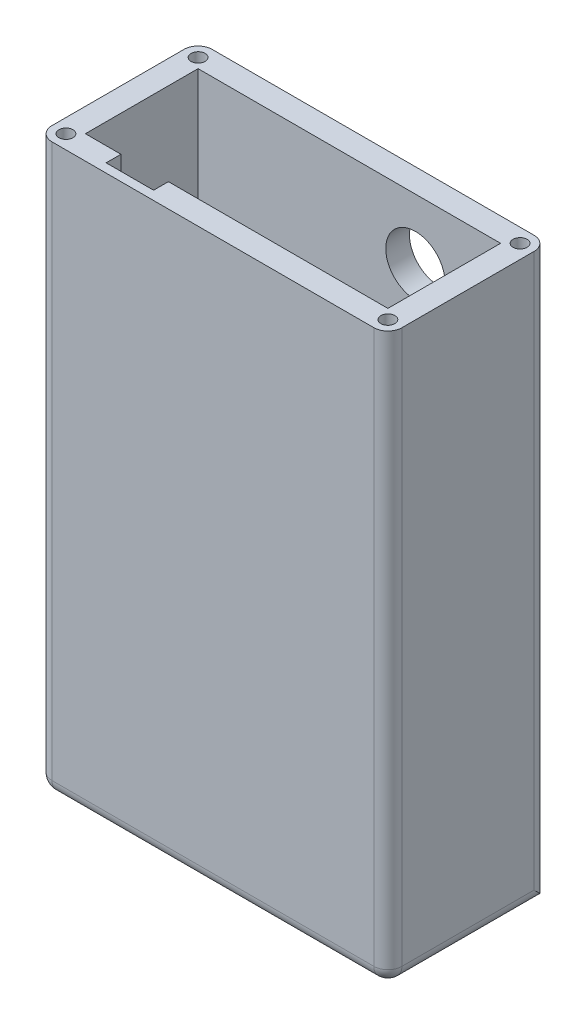
SolidWorks part; units mm, degrees
ref_plane "Front Plane" through (0, 0, 0) normal (0, 0, 1) x (1, 0, 0)
ref_plane "Top Plane" through (0, 0, 0) normal (0, 1, 0) x (1, 0, 0)
ref_plane "Right Plane" through (0, 0, 0) normal (1, 0, 0) x (0, 0, -1)
sketch "Sketch1" plane through (0, 0, 0) normal (0, 1, 0) x (1, 0, 0)
  line L1 (0, 0) -> (74.93, 0)
  line L2 (0, 0) -> (0, 34.29)
  line L3 (0, 34.29) -> (74.93, 34.29)
  line L4 (74.93, 0) -> (74.93, 34.29)
  dimension "D1" = 74.93
  dimension "D2" = 34.29
extrude "Boss-Extrude1" add sketch "Sketch1" along normal blind 87.122
shell "Shell1" thickness 2.54 removed face at (37.465, 43.561, -34.29)
sketch "Sketch12" plane through (0, 87.122, 0) normal (0, 1, 0) x (1, 0, 0)
  line L1 (0, 0) -> (74.93, 0)
  line L2 (0, 0) -> (0, 34.29)
  line L3 (0, 34.29) -> (74.93, 34.29)
  line L4 (74.93, 0) -> (74.93, 34.29)
extrude "Boss-Extrude6" add sketch "Sketch12" along normal blind 34.29
shell "Shell2" thickness 5.08 removed face at (37.465, 121.412, -17.145)
sketch "Sketch18" plane through (0, 89.662, 0) normal (0, 1, 0) x (1, 0, 0)
  line L0 (5.08, 5.08) -> (69.85, 5.08) construction
  line L1 (34.925, 5.08) -> (22.225, 5.08)
  line L2 (34.925, 5.08) -> (34.925, 14.605)
  line L3 (34.925, 14.605) -> (22.225, 14.605)
  line L4 (22.225, 5.08) -> (22.225, 14.605)
  line L5 (69.85, 5.08) -> (69.85, 29.21) construction
  line L6 (69.85, 29.21) -> (5.08, 29.21) construction
  line L7 (69.85, 22.21) -> (64.85, 22.21)
  line L8 (69.85, 22.21) -> (69.85, 12.08)
  line L9 (69.85, 12.08) -> (64.85, 12.08)
  line L10 (64.85, 22.21) -> (64.85, 12.08)
  dimension "D1" = 34.925
  dimension "D2" = 47.625
  dimension "D3" = 9.525
  dimension "D4" = 5
  dimension "D5" = 7
  dimension "D6" = 7
extrude "Cut-Extrude13" cut sketch "Sketch18" against normal up to next
sketch "Sketch20" plane through (0, 121.412, 0) normal (0, 1, 0) x (1, 0, 0)
  line L0 (0, 34.29) -> (0, 0) construction
  line L2 (74.93, 34.29) -> (0, 34.29) construction
  line L3 (0, 0) -> (74.93, 0) construction
  line L4 (74.93, 0) -> (74.93, 34.29) construction
  circle A0 centre (3, 31.29) radius 1.5
  circle A1 centre (3, 3) radius 1.5
  circle A2 centre (71.93, 3) radius 1.5
  circle A3 centre (71.93, 31.29) radius 1.5
  dimension "D1" = 3
  dimension "D2" = 3
  dimension "D3" = 3
  dimension "D4" = 3
  dimension "D5" = 3
  dimension "D6" = 3
  dimension "D7" = 3
  dimension "D8" = 3
extrude "Cut-Extrude14" cut sketch "Sketch20" against normal blind 20
fillet "Fillet1" radius 3 7 edges at (74.93, 0, -17.145) (0, 0, -17.145) (37.465, 0, 0) (74.93, 60.706, -34.29) (0, 60.706, -34.29) (74.93, 60.706, 0) (0, 60.706, 0)
sketch "Sketch22" plane through (0, 121.412, 0) normal (0, 1, 0) x (1, 0, 0)
  line L0 (5.08, 5.08) -> (69.85, 5.08) construction
  line L1 (22.86, 5.08) -> (12.7, 5.08)
  line L2 (22.86, 5.08) -> (22.86, 1.905)
  line L3 (22.86, 1.905) -> (12.7, 1.905)
  line L4 (12.7, 5.08) -> (12.7, 1.905)
  line L5 (5.08, 29.21) -> (5.08, 5.08) construction
  dimension "D1" = 3.175
  dimension "D2" = 10.16
  dimension "D3" = 17.78
extrude "Cut-Extrude15" cut sketch "Sketch22" against normal blind 31.75
sketch "Sketch23" plane through (0, 0, -34.29) normal (0, 0, -1) x (-1, 0, 0)
  line L0 (-71.93, 121.412) -> (-3, 121.412) construction
  line L1 (-71.93, 121.412) -> (-71.93, 84.582) construction
  circle A0 centre (-51.61, 108.1555) radius 6.35
  point P6 (0, 0)
  dimension "D3" = 12.7
  dimension "D1" = 13.2565
  dimension "D2" = 20.32
extrude "Cut-Extrude16" cut sketch "Sketch23" against normal up to next
